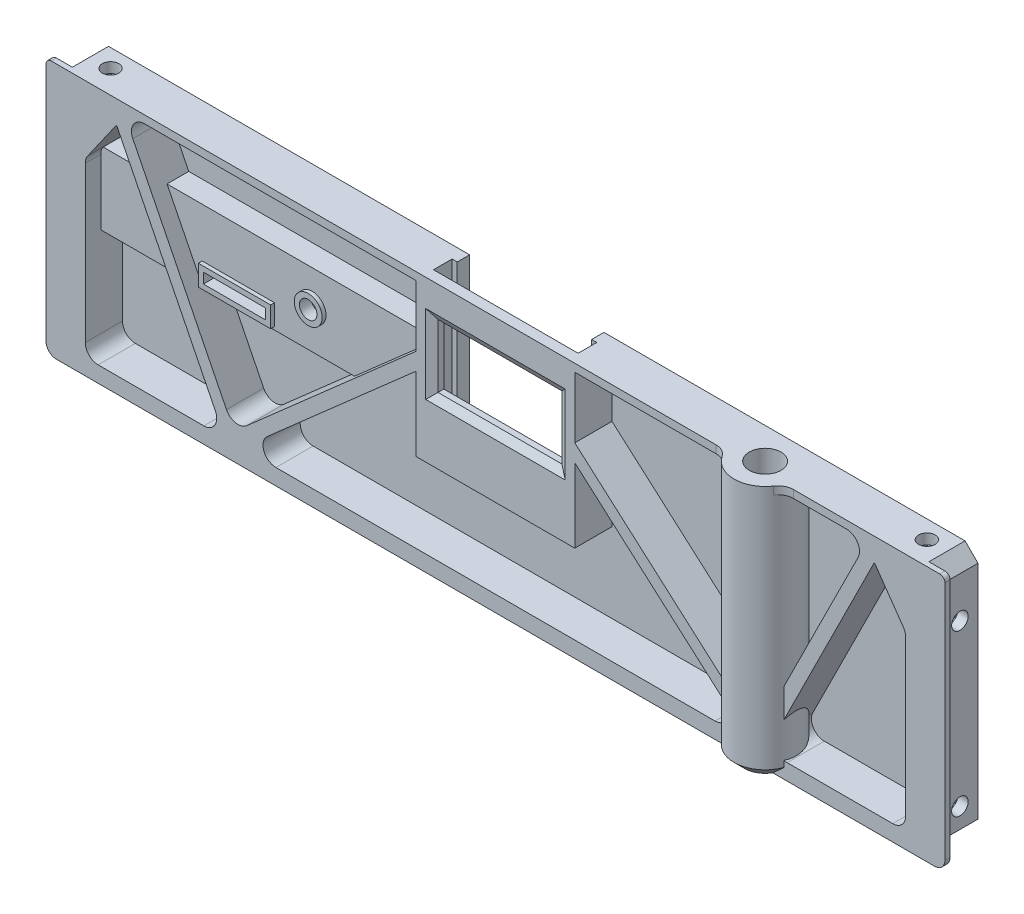
SolidWorks part; units mm, degrees
ref_plane "Front Plane" through (0, 0, 0) normal (0, 0, 1) x (1, 0, 0)
ref_plane "Top Plane" through (0, 0, 0) normal (0, 1, 0) x (1, 0, 0)
ref_plane "Right Plane" through (0, 0, 0) normal (1, 0, 0) x (0, 0, -1)
sketch "Sketch1" plane through (0, 0, 0) normal (0, 0, 1) x (1, 0, 0)
  line L1 (87, -25.55) -> (-87, -25.55)
  line L2 (87, -25.55) -> (87, 25.55)
  line L3 (87, 25.55) -> (-87, 25.55)
  line L4 (-87, -25.55) -> (-87, 25.55)
  line L5 (87, -25.55) -> (-87, 25.55) construction
  line L6 (87, 25.55) -> (-87, -25.55) construction
  point P0 (0, 0)
  dimension "D1" = 174
  dimension "D2" = 51.1
extrude "Boss-Extrude1" add sketch "Sketch1" against normal blind 8
sketch "Sketch2" plane through (0, 0, -8) normal (0, 0, -1) x (-1, 0, 0)
  line L5 (-87, -25.55) -> (-87, 25.55) construction
  line L6 (-87, 25.55) -> (87, 25.55) construction
  line L13 (85.4, -23.95) -> (85.4, 23.95)
  line L14 (-85.4, -23.95) -> (85.4, -23.95)
  line L15 (-85.4, 23.95) -> (-85.4, -23.95)
  line L16 (85.4, 23.95) -> (-85.4, 23.95)
  point P2 (0, 23.95)
  point P5 (85.4, 0)
  dimension "D1" = 1.6
  dimension "D2" = 1.6
extrude "Cut-Extrude1" cut sketch "Sketch2" against normal offset from surface (7 mm away) 1 flip side to cut up to face at (0, 0, 0)
chamfer "Chamfer1" distance 2.5 angle 45 4 edges at (-85.4, -23.95, -4.5) (-85.4, 23.95, -4.5) (85.4, -23.95, -4.5) (85.4, 23.95, -4.5)
fillet "Fillet1" radius 2 2 edges at (-87, -25.55, -0.5) (87, -25.55, -0.5)
sketch "Sketch3" plane through (0, 0, 0) normal (0, 0, 1) x (1, 0, 0)
  line L1 (-82.9, 23.95) -> (-85.4, 21.45) construction
  line L2 (-82.9, 23.95) -> (82.9, 23.95) construction
  line L3 (-82.9, 23.95) -> (-85.4, 21.45) construction
  line L4 (-82.9, 23.95) -> (82.9, 23.95) construction
  line L5 (85.4, 21.45) -> (82.9, 23.95) construction
  line L6 (85.4, 21.45) -> (85.4, -21.45) construction
  line L7 (82.9, -23.95) -> (85.4, -21.45) construction
  line L8 (82.9, -23.95) -> (-82.9, -23.95) construction
  line L9 (-85.4, -21.45) -> (-82.9, -23.95) construction
  line L10 (-85.4, -21.45) -> (-85.4, 21.45) construction
  line L11 (85.4, 21.45) -> (82.9, 23.95) construction
  line L12 (85.4, 21.45) -> (85.4, -21.45) construction
  line L13 (82.9, -23.95) -> (85.4, -21.45) construction
  line L14 (82.9, -23.95) -> (-82.9, -23.95) construction
  line L15 (-85.4, -21.45) -> (-82.9, -23.95) construction
  line L16 (-85.4, -21.45) -> (-85.4, 21.45) construction
  line L26 (79.4, -22.45) -> (-79.4, -22.45)
  line L27 (79.4, -22.45) -> (79.4, 22.45)
  line L28 (79.4, 22.45) -> (-79.4, 22.45)
  line L29 (-79.4, -22.45) -> (-79.4, 22.45)
  line L30 (79.4, -22.45) -> (-79.4, 22.45) construction
  line L31 (79.4, 22.45) -> (-79.4, -22.45) construction
  point P4 (0, 0)
  dimension "D1" = 3
  dimension "D2" = 6
extrude "Cut-Extrude2" cut sketch "Sketch3" against normal offset from surface (7.2 mm away) 0.8 up to face at (0, 0, -8)
sketch "Sketch9" plane through (0, 0, 0) normal (0, 0, 1) x (1, 0, 0)
  line L0 (-73.4, 22.45) -> (-73.4, 19.45)
  line L1 (-79.4, 22.45) -> (79.4, 22.45) construction
  line L2 (-73.4, 19.45) -> (-79.4, 10.8811)
  line L3 (-79.4, -22.45) -> (-79.4, 22.45) construction
  line L4 (-79.4, 10.8811) -> (-79.4, 22.45)
  line L5 (-79.4, 22.45) -> (-73.4, 22.45)
  dimension "D1" = 6
  dimension "D2" = 35
  dimension "D3" = 3
extrude "Boss-Extrude2" add sketch "Sketch9" against normal up to surface (7.2 mm away) up to face at (0, 0, -7.2)
hole_wizard "Ø3.0mm Dowel Hole1" positions "Sketch4" profile "Sketch5" hole size "Ø3.0" standard "ANSI Metric"
sketch "Sketch4" plane through (-85.4, 0, 0) normal (-1, 0, 0) x (0, 0, 1)
  line L0 (-4.5, 13.55) -> (-4.5, -17.55) construction
  line L2 (-8, -21.45) -> (-8, 21.45) construction
  line L4 (0, -25.55) -> (-1, -25.55) construction
  line L5 (-1, 25.55) -> (0, 25.55) construction
  point P0 (-4.5, 13.55)
  point P3 (-4.5, -17.55)
  dimension "D1" = 3.5
  dimension "D2" = 12
  dimension "D3" = 8
sketch "Sketch5" plane through (-85.4, 13.55, -4.5) normal (0, 1, 0) x (0, 0, 1)
  line L0 (0, 0) -> (0, 5)
  line L1 (0, 5) -> (1.6, 5)
  line L2 (1.6, 5) -> (1.6, 0)
  line L5 (1.6, 0) -> (0, 0)
  line L10 (0, 5) -> (-1.6, 5) construction
  line L11 (0, -6.35) -> (0, 107.95) construction
  dimension "Hole Dia." = 3.2
  dimension "Hole Depth" = 5
  dimension "Drill Angle" = 180
hole_wizard "Ø3.0mm Dowel Hole2" positions "Sketch7" profile "Sketch8" hole size "Ø3.0" standard "ANSI Metric"
sketch "Sketch7" plane through (0, 23.95, 0) normal (0, 1, 0) x (1, 0, 0)
  line L0 (-82.9, 8) -> (82.9, 8) construction
  line L2 (-87, 1) -> (-87, 0) construction
  point P0 (-79, 4.5)
  dimension "D1" = 3.5
  dimension "D2" = 8
sketch "Sketch8" plane through (-79, 23.95, -4.5) normal (1, 0, 0) x (0, 0, 1)
  line L0 (0, 0) -> (0, 5)
  line L1 (0, 5) -> (1.6, 5)
  line L2 (1.6, 5) -> (1.6, 0)
  line L5 (1.6, 0) -> (0, 0)
  line L10 (0, 5) -> (-1.6, 5) construction
  line L11 (0, -6.35) -> (0, 107.95) construction
  dimension "Hole Dia." = 3.2
  dimension "Hole Depth" = 5
  dimension "Drill Angle" = 180
sketch "Sketch10" plane through (-85.4, 0, 0) normal (-1, 0, 0) x (0, 0, 1)
  line L0 (-8, -21.45) -> (-8, 21.45) construction
  line L1 (-8, 16.3) -> (-1.75, 16.3)
  line L2 (-8, 16.3) -> (-8, 10.8)
  line L3 (-8, 10.8) -> (-1.75, 10.8)
  line L4 (-1.75, 16.3) -> (-1.75, 10.8)
  line L6 (-8, -14.8) -> (-1.75, -14.8)
  line L7 (-8, -14.8) -> (-8, -20.3)
  line L8 (-8, -20.3) -> (-1.75, -20.3)
  line L9 (-1.75, -14.8) -> (-1.75, -20.3)
  point P6 (-1.75, -17.55)
  point P8 (-1.75, 13.55)
  dimension "D1" = 5.5
  dimension "D2" = 2.75
extrude "Cut-Extrude3" cut sketch "Sketch10" against normal blind 1.8 from offset 2 offset against normal yes
sketch "Sketch11" plane through (0, 23.95, 0) normal (0, 1, 0) x (1, 0, 0)
  line L0 (-82.9, 8) -> (82.9, 8) construction
  line L1 (-81.75, 8) -> (-76.25, 8)
  line L2 (-81.75, 8) -> (-81.75, 1.75)
  line L3 (-81.75, 1.75) -> (-76.25, 1.75)
  line L4 (-76.25, 8) -> (-76.25, 1.75)
  point P6 (-79, 1.75)
  dimension "D1" = 5.5
  dimension "D2" = 2.75
extrude "Cut-Extrude4" cut sketch "Sketch11" against normal blind 1.8 from offset 2 offset against normal yes
mirror "Mirror1" about plane through (0, 0, 0) normal (1, 0, 0) of "Cut-Extrude4", "Cut-Extrude3", "Ø3.0mm Dowel Hole2", "Ø3.0mm Dowel Hole1", "Boss-Extrude2"
sketch "Sketch12" plane through (0, 0, -7.2) normal (0, 0, 1) x (1, 0, 0)
  line L0 (-73.4, 22.45) -> (-51.0137, -22.45) construction
  line L1 (-79.4, -22.45) -> (79.4, -22.45) construction
  line L2 (-51.0137, -22.45) -> (0, 22.45) construction
  line L3 (73.4, 22.45) -> (-73.4, 22.45) construction
  line L4 (0, 22.45) -> (51.0137, -22.45) construction
  line L5 (51.0137, -22.45) -> (73.4, 22.45) construction
  line L6 (-74.5187, 21.8923) -> (-51.9874, -23.2985)
  line L7 (-50.4317, -23.603) -> (0, 20.7848)
  line L8 (0, 20.7848) -> (50.4317, -23.603)
  line L9 (51.9874, -23.2985) -> (74.5187, 21.8923)
  line L10 (-72.2813, 23.0077) -> (-50.62, -20.4382)
  line L11 (-50.62, -20.4382) -> (-0.6607, 23.5337)
  line L12 (0.6607, 23.5337) -> (50.62, -20.4382)
  line L13 (50.62, -20.4382) -> (72.2813, 23.0077)
  line L14 (0, 20.7848) -> (51.4074, -24.4618) construction
  line L15 (51.4074, -24.4618) -> (74.5187, 21.8923) construction
  line L16 (-50.62, -20.4382) -> (0, 24.1152) construction
  line L17 (0, 24.1152) -> (50.62, -20.4382) construction
  line L18 (-74.5187, 21.8923) -> (-51.4074, -24.4618) construction
  line L19 (-51.4074, -24.4618) -> (0, 20.7848) construction
  line L20 (79.4, -22.45) -> (-79.4, -22.45) construction
  line L21 (-79.4, -22.45) -> (-79.4, 10.8811) construction
  arc A0 (-74.5187, 21.8923) -> (-72.2813, 23.0077) centre (-73.4, 22.45) cw
  arc A1 (74.5187, 21.8923) -> (72.2813, 23.0077) centre (73.4, 22.45) ccw
  arc A2 (50.4317, -23.603) -> (51.9874, -23.2985) centre (51.0924, -22.8524) ccw
  arc A3 (-0.6607, 23.5337) -> (0.6607, 23.5337) centre (0, 22.783) cw
  arc A4 (-51.9874, -23.2985) -> (-50.4317, -23.603) centre (-51.0924, -22.8524) ccw
  dimension "D3" = 1
  dimension "D1" = 1.25
  dimension "D2" = 26.5
extrude "Boss-Extrude3" add sketch "Sketch12" along normal up to surface (7.2 mm away) up to face at (0, 7.5828, 0)
sketch "Sketch13" plane through (0, 0, 0) normal (0, 0, 1) x (1, 0, 0)
  line L0 (-73.4, 19.45) -> (-73.4, 19.6486)
  line L1 (-73.4, 19.6486) -> (-73.301, 19.45)
  line L2 (-73.4, 19.6486) -> (-52.4104, -22.45) construction
  line L3 (-73.301, 19.45) -> (-73.4, 19.45)
  line L4 (0, 0) -> (0, 25.4565) construction
  line L5 (73.301, 19.45) -> (73.4, 19.45)
  line L6 (73.4, 19.6486) -> (73.301, 19.45)
  line L7 (73.4, 19.45) -> (73.4, 19.6486)
extrude "Small Fix" add sketch "Sketch13" against normal up to surface (7.2 mm away) up to face at (-71.6021, 1.0159, -7.2)
fillet "Fillet2" radius 2.5 15 edges at (79.4, -22.45, -3.6) (79.4, 10.8811, -3.6) (52.4104, -22.45, -3.6) (72.0032, 22.45, -3.6) (50.62, -20.4382, -3.6) (1.892, 22.45, -3.6) (49.1217, -22.45, -3.6) (0, 20.7848, -3.6) (-49.1217, -22.45, -3.6) (-1.892, 22.45, -3.6) (-50.62, -20.4382, -3.6) (-72.0032, 22.45, -3.6) (-79.4, 10.8811, -3.6) (-79.4, -22.45, -3.6) (-52.4104, -22.45, -3.6)
fillet "Fillet3" radius 0.1 4 edges at (73.4, 19.45, -3.6) (73.301, 19.45, -3.6) (-73.301, 19.45, -3.6) (-73.4, 19.45, -3.6)
sketch "Sketch14" plane through (0, 0, -8) normal (0, 0, -1) x (-1, 0, 0)
  line L1 (-13.85, 22.45) -> (13.85, 22.45) construction
  line L2 (-13.85, 22.45) -> (-13.85, -5.55) construction
  line L3 (-13.85, -5.55) -> (13.85, -5.55) construction
  line L4 (13.85, 22.45) -> (13.85, -5.55) construction
  line L5 (82.9, 23.95) -> (-82.9, 23.95) construction
  line L6 (-15.35, 23.95) -> (-15.35, -7.05)
  line L7 (-15.35, -7.05) -> (15.35, -7.05)
  line L8 (15.35, 23.95) -> (15.35, -7.05)
  line L9 (-15.35, 22.45) -> (-15.35, -7.05) construction
  line L10 (15.35, 22.45) -> (15.35, -7.05) construction
  line L11 (-15.35, 23.95) -> (15.35, 23.95)
  point P6 (0, -5.55)
  dimension "D1" = 28
  dimension "D2" = 27.7
  dimension "D3" = 1.5
  dimension "D4" = 1.5
extrude "Boss-Extrude4" add sketch "Sketch14" against normal up to surface (8 mm away) up to face at (-42.2461, 7.7039, 0)
sketch "Sketch17" plane through (0, 23.95, 0) normal (0, 1, 0) x (1, 0, 0)
  line L0 (87, 0) -> (-87, 0) construction
  line L1 (-14, 5.6) -> (14, 5.6)
  line L2 (-14, 5.6) -> (-14, 2)
  line L3 (-14, 2) -> (14, 2)
  line L4 (14, 5.6) -> (14, 2)
  point P8 (0, 2)
  point P11 (-13.85, 8)
  dimension "D1" = 3.6
  dimension "D2" = 2
  dimension "D3" = 0.15
extrude "Cut-Extrude6" cut sketch "Sketch17" against normal up to vertex (29.5 mm away) up to point (13.85, -5.55, -8)
sketch "Sketch18" plane through (0, 0, -8) normal (0, 0, -1) x (-1, 0, 0)
  line L0 (82.9, 23.95) -> (-82.9, 23.95) construction
  line L1 (-13, 23.95) -> (13, 23.95)
  line L2 (-13, 23.95) -> (-13, -2.55)
  line L3 (-13, -2.55) -> (13, -2.55)
  line L4 (13, 23.95) -> (13, -2.55)
  line L5 (-14, -5.55) -> (14, -5.55) construction
  point P6 (0, -2.55)
  dimension "D1" = 26
  dimension "D2" = 3
extrude "Cut-Extrude7" cut sketch "Sketch18" against normal up to surface (6 mm away) up to face at (0, 9.2, -2)
sketch "Sketch19" plane through (0, 0, 0) normal (0, 0, 1) x (1, 0, 0)
  line L1 (-13, 18.2) -> (13, 18.2) construction
  line L2 (-13, 18.2) -> (-13, 3.95) construction
  line L3 (-13, 3.95) -> (13, 3.95) construction
  line L4 (13, 18.2) -> (13, 3.95) construction
  line L6 (-12, 17.2) -> (12, 17.2)
  line L7 (12, 17.2) -> (12, 4.95)
  line L8 (-12, 4.95) -> (12, 4.95)
  line L9 (-12, 17.2) -> (-12, 4.95)
  dimension "D1" = 1
extrude "Cut-Extrude8" cut sketch "Sketch19" against normal up to surface (2 mm away) up to face at (0, 9.2, -2)
chamfer "Chamfer2" distance 1.5 angle 30 4 edges at (0, 4.95, 0) (-12, 11.075, 0) (12, 11.075, 0) (0, 17.2, 0) first distance on face at (0, 11.075, 0)
sketch "Sketch21" plane through (0, 0, -1) normal (0, 0, -1) x (-1, 0, 0)
  line L0 (87, -23.55) -> (87, 25.55) construction
  line L1 (-87, 25.55) -> (87, 25.55)
  line L2 (-87, 25.55) -> (-87, 23.95)
  line L3 (-87, 23.95) -> (87, 23.95)
  line L4 (87, 25.55) -> (87, 23.95)
  line L5 (82.9, 23.95) -> (-82.9, 23.95) construction
extrude "Cut-Extrude10" cut sketch "Sketch21" against normal through all
sketch "Sketch22" plane through (0, 0, 0) normal (0, 0, 1) x (1, 0, 0)
  line L0 (-79.4, -2.55) -> (-30.296, -2.55)
  line L1 (-79.4, -2.55) -> (-79.4, 11.55)
  line L2 (-79.4, 11.55) -> (-23.6, 11.55)
  line L3 (-23.6, 3.3435) -> (-23.6, 11.55) construction
  line L4 (-81.6, 0.95) -> (-25.6, 0.95) construction
  line L5 (-81.6, 0.95) -> (-81.6, 2.55) construction
  line L6 (-81.6, 2.55) -> (-25.6, 2.55) construction
  line L7 (-25.6, 0.95) -> (-25.6, 2.55) construction
  line L9 (-30.296, -2.55) -> (-15.35, 10.6048)
  line L10 (-15.35, 11.55) -> (-23.6, 11.55)
  line L12 (-15.35, 10.6048) -> (-48.1808, -18.2914) construction
  line L14 (-79.4, 10.0929) -> (-79.4, -19.95) construction
  line L15 (82.9, -23.95) -> (-82.9, -23.95) construction
  line L16 (-87, 23.95) -> (-87, -23.55) construction
  line L17 (-15.35, 10.6048) -> (-15.35, 11.55)
  line L18 (-15.35, 22.45) -> (-15.35, 10.6048) construction
  line L19 (-15.35, 10.6048) -> (-48.1808, -18.2914) construction
  dimension "D1" = 9
  dimension "D2" = 2
  dimension "D3" = 56
  dimension "D4" = 1.6
  dimension "D5" = 24.9
  dimension "D6" = 5.4
  dimension "D7" = 3.5
extrude "Boss-Extrude5" add sketch "Sketch22" against normal up to surface (7.2 mm away) from offset 3 up to face at (-71.6654, -0.5445, -7.2) offset against normal yes
sketch "Sketch23" plane through (0, 0, -8) normal (0, 0, -1) x (-1, 0, 0)
  line L1 (24.1, 10.55) -> (83.1, 10.55)
  line L2 (24.1, 10.55) -> (24.1, 0.95)
  line L3 (24.1, 0.95) -> (83.1, 0.95)
  line L4 (83.1, 10.55) -> (83.1, 0.95)
  line L5 (81.6, 0.95) -> (25.6, 0.95) construction
  line L6 (81.6, 0.95) -> (81.6, 2.55) construction
  line L7 (79.4, 11.55) -> (23.6, 11.55) construction
  point P6 (53.6, 0.95)
  point P7 (53.6, 0.95)
  dimension "D1" = 1.5
  dimension "D2" = 1
extrude "Cut-Extrude11" cut sketch "Sketch23" against normal offset from surface (3.5 mm away) 1.5 up to face at (-74.7474, 6.6091, -3)
sketch "Sketch25" plane through (0, 0, -8) normal (0, 0, -1) x (-1, 0, 0)
  line L0 (24.1, 0.95) -> (83.1, 0.95) construction
  line L1 (32.1, 0.95) -> (67.1, 0.95)
  line L2 (32.1, 0.95) -> (32.1, -1.55)
  line L3 (32.1, -1.55) -> (67.1, -1.55)
  line L4 (67.1, 0.95) -> (67.1, -1.55)
  line L5 (24.1, 10.55) -> (24.1, 0.95) construction
  line L6 (83.1, 10.55) -> (83.1, 0.95) construction
  dimension "D1" = 8
  dimension "D2" = 16
  dimension "D3" = 2.5
extrude "Cut-Extrude12" cut sketch "Sketch25" against normal up to surface (3.5 mm away) up to face at (-53.6, 5.75, -4.5)
sketch "Sketch26" plane through (0, 0, -8) normal (0, 0, -1) x (-1, 0, 0)
  line L0 (32.1, 0.95) -> (24.1, 0.95) construction
  line L1 (24.1, 10.55) -> (29.1, 10.55)
  line L2 (24.1, 10.55) -> (24.1, 3.15)
  line L3 (24.1, 3.15) -> (29.1, 3.15)
  line L4 (29.1, 10.55) -> (29.1, 3.15)
  line L5 (83.1, 10.55) -> (76.1, 10.55)
  line L6 (83.1, 10.55) -> (83.1, 3.15)
  line L7 (83.1, 3.15) -> (76.1, 3.15)
  line L8 (76.1, 10.55) -> (76.1, 3.15)
  dimension "D1" = 5
  dimension "D2" = 7
  dimension "D3" = 2.2
extrude "Boss-Extrude6" add sketch "Sketch26" against normal up to surface (3.5 mm away) up to face at (-51.6, 2.725, -4.5)
sketch "Sketch27" plane through (0, 0, -3) normal (0, 0, 1) x (1, 0, 0)
  line L0 (-47.2737, 0.435) -> (-47.2737, -0.365) construction
  line L1 (-58.2737, 0.535) -> (-47.2737, 0.535) construction
  line L2 (-58.2737, 0.535) -> (-58.2737, -0.465) construction
  line L3 (-58.2737, -0.465) -> (-47.2737, -0.465) construction
  line L4 (-47.2737, 0.535) -> (-47.2737, -0.465) construction
  line L5 (-58.2737, -0.365) -> (-58.2737, 0.435) construction
  line L8 (-57.7737, 0.535) -> (-47.7737, 0.535) construction
  line L9 (-47.7737, -0.465) -> (-57.7737, -0.465) construction
  line L10 (-58.7737, 1.035) -> (-46.7737, 1.035)
  line L11 (-46.7737, 1.035) -> (-46.7737, -0.965)
  line L12 (-58.7737, -0.965) -> (-46.7737, -0.965)
  line L13 (-58.7737, 1.035) -> (-58.7737, -0.965)
  circle A0 centre (-38.5, 4.9) radius 1.2 construction
  arc A1 (-38.5, 6.1) -> (-38.5, 3.7) centre (-38.5, 4.9) ccw construction
  circle A2 centre (-38.5, 4.9) radius 1.7
  dimension "D1" = 0.5
  dimension "D2" = 0.5
extrude "Cut-Extrude13" cut sketch "Sketch27" against normal up to surface (1.5 mm away) up to face at (-51.9333, 2.8667, -4.5)
sketch "Sketch28" plane through (0, 0, -3) normal (0, 0, 1) x (1, 0, 0)
  line L0 (-46.7737, -0.965) -> (-46.7737, 1.035) construction
  line L1 (-58.7737, -0.965) -> (-46.7737, -0.965) construction
  line L2 (-46.7737, 1.035) -> (-58.7737, 1.035) construction
  line L3 (-58.7737, 1.035) -> (-58.7737, -0.965) construction
  line L4 (-46.7737, -0.965) -> (-46.7737, 1.035)
  line L5 (-58.7737, -0.965) -> (-46.7737, -0.965)
  line L6 (-46.7737, 1.035) -> (-58.7737, 1.035)
  line L7 (-58.7737, 1.035) -> (-58.7737, -0.965)
  line L8 (-45.7737, -1.965) -> (-45.7737, 2.035)
  line L9 (-45.7737, 2.035) -> (-59.7737, 2.035)
  line L10 (-59.7737, 2.035) -> (-59.7737, -1.965)
  line L11 (-59.7737, -1.965) -> (-45.7737, -1.965)
  circle A0 centre (-38.5, 4.9) radius 1.7 construction
  circle A1 centre (-38.5, 4.9) radius 1.7
  circle A2 centre (-38.5, 4.9) radius 2.7
  dimension "D1" = 1
  dimension "D2" = 1
extrude "Boss-Extrude7" add sketch "Sketch28" along normal blind 0.75
fillet "Fillet4" radius 1 2 edges at (87, 23.95, -0.5) (-87, 23.95, -0.5)
sketch "Sketch29" plane through (0, 23.95, 0) normal (0, 1, 0) x (1, 0, 0)
  line L0 (50.195, 8) -> (50.195, 0) construction
  line L1 (13, 8) -> (82.9, 8) construction
  line L2 (86, 0) -> (-86, 0) construction
  circle A0 centre (50.195, 2) radius 3 construction
  circle A1 centre (50.195, 2) radius 6
  dimension "D1" = 6
  dimension "D2" = 12
extrude "Boss-Extrude8" add sketch "Sketch29" against normal up to surface (49.5 mm away) up to face at (0, -25.55, -0.5)
sketch "Sketch30" plane through (0, 23.95, 0) normal (0, 1, 0) x (1, 0, 0)
  circle A0 centre (50.195, 2) radius 3 construction
  circle A1 centre (50.195, 2) radius 3 construction
  circle A2 centre (50.195, 2) radius 3.075
  dimension "D1" = 6.15
extrude "Cut-Extrude14" cut sketch "Sketch30" against normal offset from surface (43.9 mm away) 4 up to face at (-18.2377, -23.95, -4.8432)
sketch "Sketch31" plane through (0, -23.95, 0) normal (0, -1, 0) x (1, 0, 0)
  line L0 (44.2789, -1) -> (-82.9, -1) construction
  line L1 (44.195, -1) -> (56.195, -1)
  line L2 (44.195, -1) -> (44.195, -8)
  line L3 (44.195, -8) -> (56.195, -8)
  line L4 (56.195, -1) -> (56.195, -8)
  line L5 (82.9, -8) -> (50.195, -8) construction
  circle A0 centre (50.195, -2) radius 6 construction
extrude "Cut-Extrude15" cut sketch "Sketch31" along normal up to surface (1.6 mm away) up to face at (25.0975, -25.55, -0.875)
chamfer "Chamfer3" distance 2 angle 45 1 edges at (50.195, -25.55, 4)
fillet "Fillet5" radius 3 2 edges at (55.8519, 23.2, 0) (44.5381, 23.2, 0)
sketch "Sketch32" plane through (0, 0, -1.75) normal (0, 0, -1) x (-1, 0, 0)
  line L1 (-81.75, 21.95) -> (-76.25, 21.95)
  line L2 (-81.75, 21.95) -> (-81.75, 20.15)
  line L3 (-81.75, 20.15) -> (-76.25, 20.15)
  line L4 (-76.25, 21.95) -> (-76.25, 20.15)
  line L5 (-83.4, 16.3) -> (-81.6, 16.3)
  line L6 (-83.4, 16.3) -> (-83.4, 10.8)
  line L7 (-83.4, 10.8) -> (-81.6, 10.8)
  line L8 (-81.6, 16.3) -> (-81.6, 10.8)
  line L9 (-83.4, -14.8) -> (-81.6, -14.8)
  line L10 (-83.4, -14.8) -> (-83.4, -20.3)
  line L11 (-83.4, -20.3) -> (-81.6, -20.3)
  line L12 (-81.6, -14.8) -> (-81.6, -20.3)
  line L13 (76.25, 21.95) -> (81.75, 21.95)
  line L14 (76.25, 21.95) -> (76.25, 20.15)
  line L15 (76.25, 20.15) -> (81.75, 20.15)
  line L16 (81.75, 21.95) -> (81.75, 20.15)
  line L17 (81.6, 16.3) -> (83.4, 16.3)
  line L18 (81.6, 16.3) -> (81.6, 10.8)
  line L19 (81.6, 10.8) -> (83.4, 10.8)
  line L20 (83.4, 16.3) -> (83.4, 10.8)
  line L21 (81.6, -14.8) -> (83.4, -14.8)
  line L22 (81.6, -14.8) -> (81.6, -20.3)
  line L23 (81.6, -20.3) -> (83.4, -20.3)
  line L24 (83.4, -14.8) -> (83.4, -20.3)
extrude "Cut-Extrude17" cut sketch "Sketch32" against normal blind 0.1
